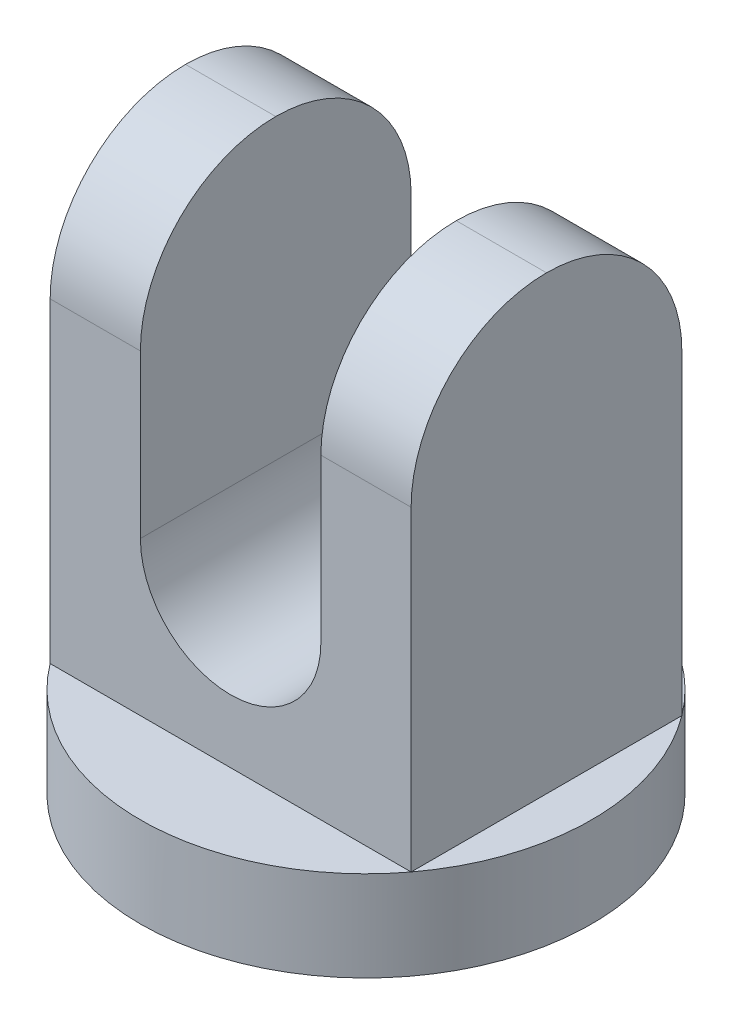
SolidWorks part; units mm, degrees
ref_plane "前视基准面" through (0, 0, 0) normal (0, 0, 1) x (1, 0, 0)
ref_plane "上视基准面" through (0, 0, 0) normal (0, 1, 0) x (1, 0, 0)
ref_plane "右视基准面" through (0, 0, 0) normal (1, 0, 0) x (0, 0, -1)
sketch "草图1" plane through (0, 0, 0) normal (0, 1, 0) x (1, 0, 0)
  line L1 (-212.8031, 131.2054) -> (212.8031, 131.2054)
  line L2 (-212.8031, 131.2054) -> (-212.8031, -131.2054)
  line L3 (-212.8031, -131.2054) -> (212.8031, -131.2054)
  line L4 (212.8031, 131.2054) -> (212.8031, -131.2054)
  line L5 (-212.8031, 131.2054) -> (212.8031, -131.2054) construction
  line L6 (-212.8031, -131.2054) -> (212.8031, 131.2054) construction
  circle A0 centre (0, 0) radius 250
extrude "凸台-拉伸1" add sketch "草图1" along normal blind 100 contours A0
sketch "草图2" plane through (0, 100, 0) normal (0, 1, 0) x (1, 0, 0)
  line L1 (-200, 150) -> (200, 150)
  line L2 (-200, 150) -> (-200, -150)
  line L3 (-200, -150) -> (200, -150)
  line L4 (200, 150) -> (200, -150)
  line L5 (-200, 150) -> (200, -150) construction
  line L6 (-200, -150) -> (200, 150) construction
  circle A0 centre (0, 0) radius 250 construction
  point P0 (0, 0)
extrude "凸台-拉伸2" add sketch "草图2" along normal blind 500
fillet "圆角1" radius 150 1 edges at (0, 600, 150)
fillet "圆角2" radius 150 1 edges at (0, 600, -150)
sketch "草图3" plane through (0, 0, 0) normal (0, 0, 1) x (1, 0, 0)
  line L0 (-200, 600) -> (200, 600) construction
  line L1 (0, 600) -> (100, 600)
  line L3 (0, 270) -> (100, 270)
  line L4 (100, 600) -> (100, 270)
  line L6 (0, 600) -> (-100, 600)
  line L8 (0, 270) -> (-100, 270)
  line L9 (-100, 600) -> (-100, 270)
  dimension "D1" = 330
  dimension "D2" = 100
extrude "切除-拉伸1" cut sketch "草图3" against normal mid plane 500
sketch "草图4" plane through (0, 0, 0) normal (0, 0, 1) x (1, 0, 0)
  line L0 (100, 270) -> (-100, 270) construction
  circle A0 centre (0, 270) radius 100
extrude "切除-拉伸2" cut sketch "草图4" against normal mid plane 500
